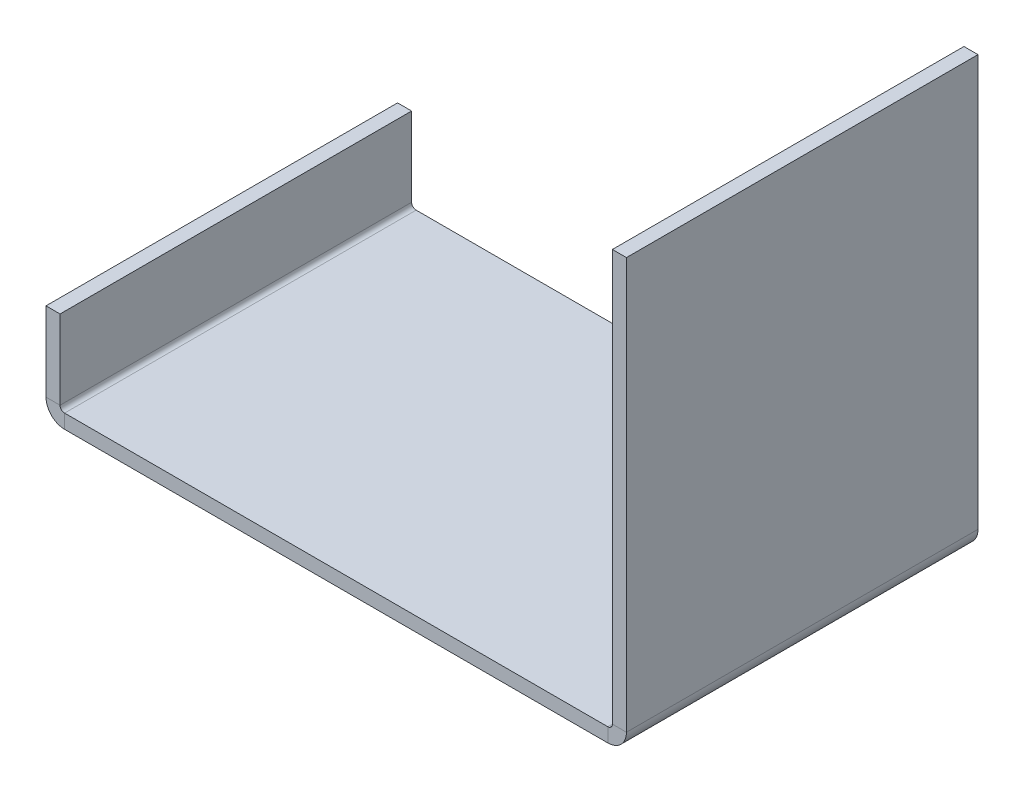
SolidWorks part; units mm, degrees
note: The reader was unsure of these and kept them because the rebuilt part matched: flange length of "Edge-Flange1", "Edge-Flange2".
ref_plane "Front Plane" through (0, 0, 0) normal (0, 0, 1) x (1, 0, 0)
ref_plane "Top Plane" through (0, 0, 0) normal (0, 1, 0) x (1, 0, 0)
ref_plane "Right Plane" through (0, 0, 0) normal (1, 0, 0) x (0, 0, -1)
sketch "Sketch1" plane through (0, 0, 0) normal (0, 1, 0) x (1, 0, 0)
  line L1 (-47.1805, -28.575) -> (47.1805, -28.575)
  line L2 (-47.1805, -28.575) -> (-47.1805, 28.575)
  line L3 (-47.1805, 28.575) -> (47.1805, 28.575)
  line L4 (47.1805, -28.575) -> (47.1805, 28.575)
  line L5 (-47.1805, -28.575) -> (47.1805, 28.575) construction
  line L6 (-47.1805, 28.575) -> (47.1805, -28.575) construction
  point P0 (0, 0)
  dimension "D1" = 94.361
  dimension "D2" = 57.15
base flange "Base-Flange1" sketch "Sketch1" thickness 2.286 reverse thickness direction no parameters "D1"=0.7366
edge flange "Edge-Flange1" sketch "Sketch11" flange angle 90 flange length 15.875 flange position material inside bend radius 0.7366 thickness 2.286 relief rectangular parameters "D6"=10, "D8"=0.254
sketch "Sketch11" plane through (-47.1805, 0, 0) normal (-1, 0, 0) x (0, 0, 1)
  line L2 (-28.575, 0) -> (-28.575, 13.589)
  line L3 (-28.575, 13.589) -> (28.575, 13.589)
  line L4 (28.575, 13.589) -> (28.575, 0)
  line L11 (-28.575, 0) -> (28.575, 0) construction
  line L12 (-28.575, 0) -> (28.575, 0)
bend "EdgeBend2" bend radius 0.7366 bend angle 90 parameters "D5"=2
edge flange "Edge-Flange2" sketch "Sketch14" flange angle 90 flange length 69.85 flange position material inside bend radius 0.7366 thickness 2.286 relief rectangular parameters "D6"=10
sketch "Sketch14" plane through (47.1805, 0, 0) normal (1, 0, 0) x (0, 0, -1)
  line L2 (-28.575, 0) -> (-28.575, 67.564)
  line L3 (-28.575, 67.564) -> (28.575, 67.564)
  line L4 (28.575, 67.564) -> (28.575, 0)
  line L7 (-28.575, 0) -> (28.575, 0) construction
  line L8 (-28.575, 0) -> (28.575, 0)
bend "EdgeBend3" bend radius 0.7366 bend angle 90 parameters "D5"=3
sketch "Bend-Lines1" [suppressed] plane through (0, 0, 0) normal (0, 1, 0) x (1, 0, 0)
sketch "Bounding-Box1" [suppressed] plane through (0, 0, 0) normal (0, 1, 0) x (1, 0, 0)
sheet metal parameters "Sheet-Metal1" thickness 2.286 parameters "D1"=0.7366
flat pattern "Flat-Pattern1" [suppressed]
sketch "Bend-Lines2" plane through (0, 0, 0) normal (0, 1, 0) x (1, 0, 0)
sketch3d "Bounding-Box2" [suppressed]
  line L0 (45.2437, -50.8, 0) -> (45.2437, 50.8, 0) construction
  line L1 (-45.2438, -50.8, 0) -> (-45.2438, 50.8, 0) construction
  line L2 (45.2437, -50.8, 0) -> (-45.2438, -50.8, 0) construction
  line L3 (45.2437, 50.8, 0) -> (-45.2438, 50.8, 0) construction
sheet metal parameters "Sheet-Metal2" thickness 2.286 parameters "D1"=0.7366
flat pattern "Flat-Pattern1"
sketch "Bend-Lines2" plane through (0, 0, 0) normal (0, 1, 0) x (1, 0, 0)
  line L0 (-56.8579, 28.575) -> (-56.8579, -28.575) construction
  line L2 (-56.8579, 28.575) -> (-56.8579, -28.575) construction
  point P2 (56.8579, -28.575)
  point P3 (56.8579, 28.575)
sketch3d "Bounding-Box2" [suppressed]
  line L0 (47.1805, 28.575, 0) -> (-117.3353, 28.575, 0) construction
  line L1 (47.1805, -28.575, 0) -> (-117.3353, -28.575, 0) construction
  line L2 (47.1805, 28.575, 0) -> (47.1805, -28.575, 0) construction
  line L3 (-117.3353, 28.575, 0) -> (-117.3353, -28.575, 0) construction
bend of the flat pattern "Flatten-<EdgeBend2>1"
sheet metal parameters "Sheet-Metal3" thickness 2.286 parameters "D1"=0.7366
flat pattern "Flat-Pattern1"
sketch "Bend-Lines2" plane through (0, 0, 0) normal (0, 1, 0) x (1, 0, 0)
  line L0 (-56.8579, 28.575) -> (-56.8579, -28.575) construction
  line L1 (56.8579, -28.575) -> (56.8579, 28.575) construction
  line L2 (-56.8579, 28.575) -> (-56.8579, -28.575) construction
  line L3 (56.8579, -28.575) -> (56.8579, 28.575) construction
sketch3d "Bounding-Box2" [suppressed]
  line L0 (136.3853, 28.575, 0) -> (-82.4103, 28.575, 0) construction
  line L1 (136.3853, -28.575, 0) -> (-82.4103, -28.575, 0) construction
  line L2 (136.3853, 28.575, 0) -> (136.3853, -28.575, 0) construction
  line L3 (-82.4103, 28.575, 0) -> (-82.4103, -28.575, 0) construction
bend of the flat pattern "Flatten-<EdgeBend2>1"
bend of the flat pattern "Flatten-<EdgeBend3>1"
